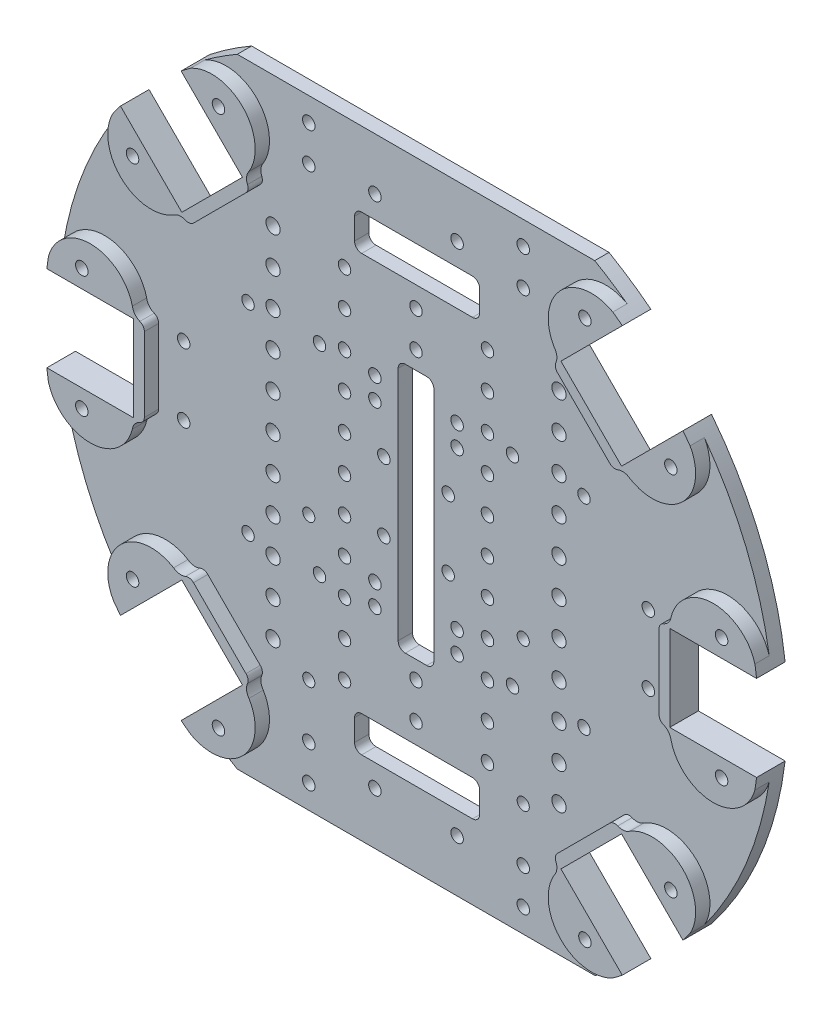
SolidWorks part; units mm, degrees
ref_plane "Front Plane" through (0, 0, 0) normal (0, 0, 1) x (1, 0, 0)
ref_plane "Top Plane" through (0, 0, 0) normal (0, 1, 0) x (1, 0, 0)
ref_plane "Right Plane" through (0, 0, 0) normal (1, 0, 0) x (0, 0, -1)
sketch "Sketch1" plane through (0, 0, 0) normal (0, 0, 1) x (1, 0, 0)
  line L0 (0, 0) -> (0, 100) construction
  line L5 (44.5477, 61.5183) -> (61.7144, 78.685)
  line L6 (44.5477, 61.5183) -> (61.5183, 44.5477)
  line L7 (-12, 75) -> (12, 75) construction
  line L8 (-12, 75) -> (-12, 99.2774) construction
  line L9 (12, 75) -> (12, 99.2774) construction
  line L10 (-17, 89.5) -> (17, 89.5) construction
  line L11 (61.5183, 44.5477) -> (78.685, 61.7144)
  line L12 (75, 12) -> (99.2774, 12)
  line L13 (75, 12) -> (75, -12)
  line L14 (75, -12) -> (99.2774, -12)
  line L15 (61.5183, -44.5477) -> (78.685, -61.7144)
  line L16 (61.5183, -44.5477) -> (44.5477, -61.5183)
  line L17 (44.5477, -61.5183) -> (61.7144, -78.685)
  line L18 (12, -75) -> (12, -99.2774) construction
  line L19 (12, -75) -> (-12, -75) construction
  line L20 (-12, -75) -> (-12, -99.2774) construction
  line L21 (-44.5477, -61.5183) -> (-61.7144, -78.685)
  line L22 (-44.5477, -61.5183) -> (-61.5183, -44.5477)
  line L23 (-61.5183, -44.5477) -> (-78.685, -61.7144)
  line L24 (-75, -12) -> (-99.2774, -12)
  line L25 (-75, -12) -> (-75, 12)
  line L26 (-75, 12) -> (-99.2774, 12)
  line L27 (-61.5183, 44.5477) -> (-78.685, 61.7144)
  line L28 (-61.5183, 44.5477) -> (-44.5477, 61.5183)
  line L29 (-44.5477, 61.5183) -> (-61.7144, 78.685)
  circle A1 centre (0, 0) radius 100
  circle A2 centre (-17, 89.5) radius 1.75 construction
  circle A3 centre (17, 89.5) radius 1.75 construction
  circle A4 centre (51.2652, 75.3069) radius 1.75
  circle A5 centre (75.3069, 51.2652) radius 1.75
  circle A6 centre (89.5, 17) radius 1.75
  circle A7 centre (89.5, -17) radius 1.75
  circle A8 centre (75.3069, -51.2652) radius 1.75
  circle A9 centre (51.2652, -75.3069) radius 1.75
  circle A10 centre (17, -89.5) radius 1.75 construction
  circle A11 centre (-17, -89.5) radius 1.75 construction
  circle A12 centre (-51.2652, -75.3069) radius 1.75
  circle A13 centre (-75.3069, -51.2652) radius 1.75
  circle A14 centre (-89.5, -17) radius 1.75
  circle A15 centre (-89.5, 17) radius 1.75
  circle A16 centre (-75.3069, 51.2652) radius 1.75
  circle A17 centre (-51.2652, 75.3069) radius 1.75
  point P2 (0, 89.5)
  point P4 (0, 75)
  point P12 (0, 75)
  point P19 (0, 89.5)
  dimension "150" = 200
  dimension "D7" = 3.5
  dimension "D2" = 25
  dimension "D3" = 8
  dimension "D4" = 24
  dimension "D5" = 14.5
  dimension "D6" = 34
extrude "Boss-Extrude1" add sketch "Sketch1" along normal blind 4 contours L12 A1 L11 L6 L5 L29 L28 L27 L26 L25 L24 L23 L22 L21 L17 L16 L15 L14 L13 A15 A14 A9 A8 A5 A4 A6 A7 A12 A13 A16 A17 region at (0, 0, 0)
sketch "Sketch2" plane through (0, 0, 4) normal (0, 0, 1) x (1, 0, 0)
  line L0 (0, 35) -> (0, -35) construction
  line L1 (-35, 35) -> (35, 35) construction
  line L2 (-35, 35) -> (-35, -35) construction
  line L3 (-35, -35) -> (35, -35) construction
  line L4 (35, 35) -> (35, -35) construction
  line L5 (-35, 35) -> (35, -35) construction
  line L6 (-35, -35) -> (35, 35) construction
  line L7 (0, 35) -> (0, 80)
  line L8 (-30, -15) -> (30, -15) construction
  line L9 (-30, -15) -> (-30, -55) construction
  line L10 (-30, -55) -> (30, -55) construction
  line L11 (30, -15) -> (30, -55) construction
  line L12 (-30, -15) -> (30, -55) construction
  line L13 (-30, -55) -> (30, -15) construction
  line L14 (-30, 80) -> (30, 80)
  line L15 (0, -55) -> (0, -80)
  line L16 (30, -80) -> (-30, -80)
  line L17 (0, 0) -> (-40, 0) construction
  line L18 (0, 0) -> (40, 0) construction
  line L19 (0, 10) -> (-40, 10)
  line L20 (0, 10) -> (40, 10)
  line L21 (0, 20) -> (-40, 20)
  line L22 (0, 20) -> (40, 20)
  line L23 (0, 30) -> (-40, 30)
  line L24 (0, 30) -> (40, 30)
  line L25 (0, 40) -> (-40, 40)
  line L26 (0, 40) -> (40, 40)
  line L27 (0, 50) -> (-40, 50)
  line L28 (0, 50) -> (40, 50)
  line L29 (0, -10) -> (40, -10)
  line L30 (0, -10) -> (-40, -10)
  line L31 (0, -20) -> (40, -20)
  line L32 (0, -20) -> (-40, -20)
  line L33 (0, -30) -> (40, -30)
  line L34 (0, -30) -> (-40, -30)
  line L35 (0, -40) -> (40, -40)
  line L36 (0, -40) -> (-40, -40)
  line L37 (0, -50) -> (40, -50)
  line L38 (0, -50) -> (-40, -50)
  line L39 (30, -70) -> (-30, -70)
  line L40 (-30, 70) -> (30, 70)
  circle A0 centre (0, 0) radius 100
  circle A1 centre (-30, -55) radius 1.7
  circle A2 centre (-30, -15) radius 1.7
  circle A3 centre (30, -55) radius 1.7
  circle A4 centre (30, -15) radius 1.7
  circle A5 centre (-30, 80) radius 1.75
  circle A6 centre (30, 80) radius 1.75
  circle A7 centre (-30, -80) radius 1.75
  circle A8 centre (30, -80) radius 1.75
  circle A9 centre (-40, 0) radius 2
  circle A10 centre (-20, 0) radius 1.75
  circle A11 centre (0, 0) radius 1.75
  circle A12 centre (40, 0) radius 2
  circle A13 centre (20, 0) radius 1.75
  circle A14 centre (20, 10) radius 1.75
  circle A15 centre (40, 10) radius 2
  circle A16 centre (-20, 10) radius 1.75
  circle A17 centre (-40, 10) radius 2
  circle A18 centre (0, 10) radius 1.75
  circle A19 centre (20, 20) radius 1.75
  circle A20 centre (40, 20) radius 2
  circle A21 centre (-20, 20) radius 1.75
  circle A22 centre (-40, 20) radius 2
  circle A23 centre (0, 20) radius 1.75
  circle A24 centre (20, 30) radius 1.75
  circle A25 centre (40, 30) radius 2
  circle A26 centre (-20, 30) radius 1.75
  circle A27 centre (-40, 30) radius 2
  circle A28 centre (0, 30) radius 1.75
  circle A29 centre (20, 40) radius 1.75
  circle A30 centre (40, 40) radius 2
  circle A31 centre (-20, 40) radius 1.75
  circle A32 centre (-40, 40) radius 2
  circle A33 centre (0, 40) radius 1.75
  circle A34 centre (20, 50) radius 1.75
  circle A35 centre (40, 50) radius 2
  circle A36 centre (-20, 50) radius 1.75
  circle A37 centre (-40, 50) radius 2
  circle A38 centre (0, 50) radius 1.75
  circle A39 centre (40, -10) radius 2
  circle A40 centre (0, -10) radius 1.75
  circle A41 centre (20, -10) radius 1.75
  circle A42 centre (-20, -10) radius 1.75
  circle A43 centre (-40, -10) radius 2
  circle A44 centre (40, -20) radius 2
  circle A45 centre (0, -20) radius 1.75
  circle A46 centre (20, -20) radius 1.75
  circle A47 centre (-20, -20) radius 1.75
  circle A48 centre (-40, -20) radius 2
  circle A49 centre (40, -30) radius 2
  circle A50 centre (0, -30) radius 1.75
  circle A51 centre (20, -30) radius 1.75
  circle A52 centre (-20, -30) radius 1.75
  circle A53 centre (-40, -30) radius 2
  circle A54 centre (40, -40) radius 2
  circle A55 centre (0, -40) radius 1.75
  circle A56 centre (20, -40) radius 1.75
  circle A57 centre (-20, -40) radius 1.75
  circle A58 centre (-40, -40) radius 2
  circle A59 centre (40, -50) radius 2
  circle A60 centre (0, -50) radius 1.75
  circle A61 centre (20, -50) radius 1.75
  circle A62 centre (-20, -50) radius 1.75
  circle A63 centre (-40, -50) radius 2
  circle A64 centre (30, -70) radius 1.75
  circle A65 centre (-30, -70) radius 1.75
  circle A66 centre (-30, 70) radius 1.75
  circle A67 centre (30, 70) radius 1.75
  point P10 (0, 0)
  point P23 (0, 80)
  point P30 (0, -80)
  dimension "D1" = 200
  dimension "D6" = 3.4
  dimension "D9" = 3.5
  dimension "D10" = 3.5
  dimension "D13" = 3.5
  dimension "D14" = 3.5
  dimension "D16" = 4
  dimension "D17" = 3.5
  dimension "D18" = 3.5
  dimension "D2" = 70
  dimension "D3" = 70
  dimension "D4" = 40
  dimension "D5" = 60
  dimension "D7" = 45
  dimension "D8" = 60
  dimension "D11" = 25
  dimension "D12" = 60
  dimension "D15" = 40
  dimension "D19" = 6
  dimension "D20" = 6
  dimension "D21" = 2
  dimension "D22" = 2
extrude "Cut-Extrude1" cut sketch "Sketch2" against normal blind 10 contours A65 | A7 | A8 | A64 | A3 | A59 | A61 L37 | A61 L37 | A63 | L38 A62 | L38 A62 | L37 A60 L38 | L38 A60 L37 | A58 | L36 A57 | L36 A57 | L35 A55 L36 | L36 A55 L35 | A56 L35 | A56 L35 | A54 | A49 | A51 L33 | A51 L33 | L34 A50 L33 | L33 A50 L34 | L34 A52 | L34 A52 | A53 | A48 | L32 A47 | L32 A47 | L31 A45 L32 | L32 A45 L31 | A46 L31 | A46 L31 | A44 | A4 | A2 | L30 A42 | L30 A42 | A43 | L30 A40 L29 | L29 A40 L30 | A41 L29 | A41 L29 | A39 | A12 | A13 | A11 | A9 | A10 | A15 | A14 L20 | A14 L20 | L19 A18 L20 | L20 A18 L19 | L19 A16 | L19 A16 | A17 | A22 | A21 | A23 | A19 | A25 | A30 | A35 | A29 | A33 | A31 | A32 | A27 | A26 | A28 | A24 | A20 | A38 | A36 | A37 | A34 | A1 | A6 | A67 | A66 | A5 region at (30, -78.2995, 4) region at (-31.7005, -80, 4) region at (30, -68.2995, 4) region at (-31.7005, -70, 4) region at (0, 9.2573, 4) region at (0, 10.7427, 4) region at (-41.9434, 10, 4) region at (-20, 9.2573, 4) region at (-20, 10.7427, 4) region at (40, 11.9434, 4) region at (20, 10.7427, 4) region at (20, 9.2573, 4) region at (0, -9.2573, 4) region at (0, -10.7427, 4) region at (40, -8.0566, 4) region at (20, -9.2573, 4) region at (20, -10.7427, 4) region at (-41.9434, -10, 4) region at (-20, -10.7427, 4) region at (-20, -9.2573, 4) region at (0, -19.2573, 4) region at (0, -20.7427, 4) region at (40, -18.0566, 4) region at (20, -19.2573, 4) region at (20, -20.7427, 4) region at (-41.9434, -20, 4) region at (-20, -20.7427, 4) region at (-20, -19.2573, 4) region at (0, -29.2573, 4) region at (0, -30.7427, 4) region at (40, -28.0566, 4) region at (20, -29.2573, 4) region at (20, -30.7427, 4) region at (-41.9434, -30, 4) region at (-20, -30.7427, 4) region at (-20, -29.2573, 4) region at (0, -39.2573, 4) region at (0, -40.7427, 4) region at (40, -38.0566, 4) region at (20, -39.2573, 4) region at (20, -40.7427, 4) region at (-41.9434, -40, 4) region at (-20, -40.7427, 4) region at (-20, -39.2573, 4) region at (0, -49.2573, 4) region at (0, -50.7427, 4) region at (40, -48.0566, 4) region at (20, -49.2573, 4) region at (20, -50.7427, 4) region at (-41.9434, -50, 4) region at (-20, -50.7427, 4) region at (-20, -49.2573, 4) region at (-30, -15, 4) region at (30, -55, 4) region at (30, -15, 4) region at (-40, 0, 4) region at (-20, 0, 4) region at (0, 0, 4) region at (40, 0, 4) region at (20, 0, 4)
sketch "Sketch3" plane through (0, 0, 4) normal (0, 0, 1) x (1, 0, 0)
  line L0 (-78.685, 61.7144) -> (-61.5183, 44.5477)
  line L1 (-61.5183, 44.5477) -> (-44.5477, 61.5183)
  line L2 (-44.5477, 61.5183) -> (-61.7144, 78.685)
  line L3 (-58.255, 43.5684) -> (-43.5684, 58.255)
  line L4 (-53.033, 53.033) -> (-50.9117, 50.9117)
  line L5 (-10.385, 72) -> (10.385, 72)
  line L6 (-12, 75) -> (12, 75)
  line L7 (-12, 99.2774) -> (-12, 75)
  line L8 (12, 75) -> (12, 99.2774)
  line L9 (43.5684, 58.255) -> (58.255, 43.5684)
  line L10 (44.5477, 61.5183) -> (61.5183, 44.5477)
  line L11 (61.7144, 78.685) -> (44.5477, 61.5183)
  line L12 (61.5183, 44.5477) -> (78.685, 61.7144)
  line L13 (72, 10.385) -> (72, -10.385)
  line L14 (75, 12) -> (75, -12)
  line L15 (99.2774, 12) -> (75, 12)
  line L16 (75, -12) -> (99.2774, -12)
  line L17 (58.255, -43.5684) -> (43.5684, -58.255)
  line L18 (61.5183, -44.5477) -> (44.5477, -61.5183)
  line L19 (78.685, -61.7144) -> (61.5183, -44.5477)
  line L20 (44.5477, -61.5183) -> (61.7144, -78.685)
  line L21 (10.385, -72) -> (-10.385, -72)
  line L22 (12, -75) -> (-12, -75)
  line L23 (12, -99.2774) -> (12, -75)
  line L24 (-12, -75) -> (-12, -99.2774)
  line L25 (-43.5684, -58.255) -> (-58.255, -43.5684)
  line L26 (-44.5477, -61.5183) -> (-61.5183, -44.5477)
  line L27 (-61.7144, -78.685) -> (-44.5477, -61.5183)
  line L28 (-61.5183, -44.5477) -> (-78.685, -61.7144)
  line L29 (-72, -10.385) -> (-72, 10.385)
  line L30 (-75, -12) -> (-75, 12)
  line L31 (-99.2774, -12) -> (-75, -12)
  line L32 (-75, 12) -> (-99.2774, 12)
  arc A1 (-12.2421, 73.2574) -> (-10.385, 72) centre (-10.385, 74) ccw
  circle A2 centre (0, 0) radius 100
  arc A3 (-61.5183, 44.5477) -> (-78.685, 61.7144) centre (-70.1016, 53.1311) cw
  arc A4 (-61.7144, 78.685) -> (-44.5477, 61.5183) centre (-53.1311, 70.1016) cw
  circle A5 centre (-51.2652, 75.3069) radius 1.75
  circle A6 centre (-75.3069, 51.2652) radius 1.75
  arc A7 (-43.1444, 60.4573) -> (-42.7452, 63.8182) centre (-40.0316, 61.7918) cw
  arc A8 (-60.4573, 43.1444) -> (-63.8182, 42.7452) centre (-61.7918, 40.0316) ccw
  arc A9 (-60.4573, 43.1444) -> (-58.255, 43.5684) centre (-59.6692, 44.9826) ccw
  arc A10 (-43.1444, 60.4573) -> (-43.5684, 58.255) centre (-44.9826, 59.6692) cw
  arc A11 (-12.2421, 73.2574) -> (-14.9009, 75.3517) centre (-15.3867, 72) ccw
  arc A12 (-12, 75) -> (-12, 99.2774) centre (-12, 87.1387) cw
  circle A13 centre (-17, 89.5) radius 1.75
  circle A14 centre (17, 89.5) radius 1.75
  arc A15 (12, 99.2774) -> (12, 75) centre (12, 87.1387) cw
  arc A16 (12.2421, 73.2574) -> (14.9009, 75.3517) centre (15.3867, 72) cw
  arc A17 (12.2421, 73.2574) -> (10.385, 72) centre (10.385, 74) cw
  arc A18 (43.1444, 60.4573) -> (43.5684, 58.255) centre (44.9826, 59.6692) ccw
  arc A19 (43.1444, 60.4573) -> (42.7452, 63.8182) centre (40.0316, 61.7918) ccw
  arc A20 (44.5477, 61.5183) -> (61.7144, 78.685) centre (53.1311, 70.1016) cw
  circle A21 centre (51.2652, 75.3069) radius 1.75
  circle A22 centre (75.3069, 51.2652) radius 1.75
  arc A23 (78.685, 61.7144) -> (61.5183, 44.5477) centre (70.1016, 53.1311) cw
  arc A24 (60.4573, 43.1444) -> (63.8182, 42.7452) centre (61.7918, 40.0316) cw
  arc A25 (60.4573, 43.1444) -> (58.255, 43.5684) centre (59.6692, 44.9826) cw
  arc A26 (73.2574, 12.2421) -> (72, 10.385) centre (74, 10.385) ccw
  arc A27 (73.2574, 12.2421) -> (75.3517, 14.9009) centre (72, 15.3867) ccw
  arc A28 (75, 12) -> (99.2774, 12) centre (87.1387, 12) cw
  circle A29 centre (89.5, 17) radius 1.75
  circle A30 centre (89.5, -17) radius 1.75
  arc A31 (99.2774, -12) -> (75, -12) centre (87.1387, -12) cw
  arc A32 (73.2574, -12.2421) -> (75.3517, -14.9009) centre (72, -15.3867) cw
  arc A33 (73.2574, -12.2421) -> (72, -10.385) centre (74, -10.385) cw
  arc A34 (60.4573, -43.1444) -> (58.255, -43.5684) centre (59.6692, -44.9826) ccw
  arc A35 (60.4573, -43.1444) -> (63.8182, -42.7452) centre (61.7918, -40.0316) ccw
  arc A36 (61.5183, -44.5477) -> (78.685, -61.7144) centre (70.1016, -53.1311) cw
  circle A37 centre (75.3069, -51.2652) radius 1.75
  circle A38 centre (51.2652, -75.3069) radius 1.75
  arc A39 (61.7144, -78.685) -> (44.5477, -61.5183) centre (53.1311, -70.1016) cw
  arc A40 (43.1444, -60.4573) -> (42.7452, -63.8182) centre (40.0316, -61.7918) cw
  arc A41 (43.1444, -60.4573) -> (43.5684, -58.255) centre (44.9826, -59.6692) cw
  arc A42 (12.2421, -73.2574) -> (10.385, -72) centre (10.385, -74) ccw
  arc A43 (12.2421, -73.2574) -> (14.9009, -75.3517) centre (15.3867, -72) ccw
  arc A44 (12, -75) -> (12, -99.2774) centre (12, -87.1387) cw
  circle A45 centre (17, -89.5) radius 1.75
  circle A46 centre (-17, -89.5) radius 1.75
  arc A47 (-12, -99.2774) -> (-12, -75) centre (-12, -87.1387) cw
  arc A48 (-12.2421, -73.2574) -> (-14.9009, -75.3517) centre (-15.3867, -72) cw
  arc A49 (-12.2421, -73.2574) -> (-10.385, -72) centre (-10.385, -74) cw
  arc A50 (-43.1444, -60.4573) -> (-43.5684, -58.255) centre (-44.9826, -59.6692) ccw
  arc A51 (-43.1444, -60.4573) -> (-42.7452, -63.8182) centre (-40.0316, -61.7918) ccw
  arc A52 (-44.5477, -61.5183) -> (-61.7144, -78.685) centre (-53.1311, -70.1016) cw
  circle A53 centre (-51.2652, -75.3069) radius 1.75
  circle A54 centre (-75.3069, -51.2652) radius 1.75
  arc A55 (-78.685, -61.7144) -> (-61.5183, -44.5477) centre (-70.1016, -53.1311) cw
  arc A56 (-60.4573, -43.1444) -> (-63.8182, -42.7452) centre (-61.7918, -40.0316) cw
  arc A57 (-60.4573, -43.1444) -> (-58.255, -43.5684) centre (-59.6692, -44.9826) cw
  arc A58 (-73.2574, -12.2421) -> (-72, -10.385) centre (-74, -10.385) ccw
  arc A59 (-73.2574, -12.2421) -> (-75.3517, -14.9009) centre (-72, -15.3867) ccw
  arc A60 (-75, -12) -> (-99.2774, -12) centre (-87.1387, -12) cw
  circle A61 centre (-89.5, -17) radius 1.75
  circle A62 centre (-89.5, 17) radius 1.75
  arc A63 (-99.2774, 12) -> (-75, 12) centre (-87.1387, 12) cw
  arc A64 (-73.2574, 12.2421) -> (-75.3517, 14.9009) centre (-72, 15.3867) cw
  arc A65 (-73.2574, 12.2421) -> (-72, 10.385) centre (-74, 10.385) cw
  point P29 (-59.397, 42.4264)
  point P32 (-42.4264, 59.397)
  dimension "D2" = 2
  dimension "D1" = 2
  dimension "D3" = 8
extrude "Boss-Extrude2" add sketch "Sketch3" along normal blind 4 contours A39 A40 A2 L20 A38 | A41 A40 A39 L18 A36 A35 A34 L17 | A36 L19 A2 A35 A37 | A31 A32 A2 L16 A30 | A33 A32 A31 L14 A28 A27 A26 L13 | A28 L15 A2 A27 A29 | A23 A24 A2 L12 A22 | A25 A24 A23 L10 A20 A19 A18 L9 | A20 L11 A2 A19 A21 | A4 A7 A2 L2 A5 | A10 A7 A4 L1 L4 L3 | A8 A9 L3 L4 L1 A3 | A8 A3 L0 A2 A6 | A63 A64 A2 L32 A62 | A65 A64 A63 L30 A60 A59 A58 L29 | A60 L31 A2 A59 A61 | A55 A56 A2 L28 A54 | A57 A56 A55 L26 A52 A51 A50 L25 | A52 L27 A2 A51 A53 region at (-73.6709, 49.4003, 4) region at (-56.4143, 47.6048, 4) region at (-49.4003, 73.6709, 4) region at (-47.6048, 56.4143, 4) region at (-87.0245, 17.1619, 4) region at (-73.5526, 0, 4) region at (-87.0245, -17.1619, 4) region at (-73.6709, -49.4003, 4) region at (49.4003, 73.6709, 4) region at (-52.0095, -52.0095, 4) region at (-49.4003, -73.6709, 4) region at (52.0095, 52.0095, 4) region at (73.6709, 49.4003, 4) region at (87.0245, 17.1619, 4) region at (73.5526, 0, 4) region at (87.0245, -17.1619, 4) region at (49.4003, -73.6709, 4) region at (73.6709, -49.4003, 4) region at (52.0095, -52.0095, 4)
sketch "Sketch4" plane through (0, 0, 0) normal (0, 0, -1) x (-1, 0, 0)
  line L0 (-11.5, 72) -> (-11.5, 28)
  line L1 (-11.5, 22) -> (11.5, 22) construction
  line L2 (-11.5, 22) -> (-11.5, -22) construction
  line L3 (-11.5, -22) -> (11.5, -22) construction
  line L4 (11.5, 22) -> (11.5, -22) construction
  line L5 (-11.5, 22) -> (11.5, -22) construction
  line L6 (-11.5, -22) -> (11.5, 22) construction
  line L7 (-11.5, 72) -> (11.5, 72)
  line L8 (11.5, 72) -> (11.5, 28)
  line L9 (-11.5, 28) -> (11.5, 28)
  line L10 (-11.5, 22) -> (-11.5, -22)
  line L11 (-11.5, 22) -> (11.5, 22)
  line L12 (11.5, 22) -> (11.5, -22)
  line L13 (-11.5, -22) -> (11.5, -22)
  line L14 (-11.5, -28) -> (-11.5, -72)
  line L15 (-11.5, -28) -> (11.5, -28)
  line L16 (11.5, -28) -> (11.5, -72)
  line L17 (-11.5, -72) -> (11.5, -72)
  line L18 (0, 0) -> (100, 0)
  line L19 (-47, 28) -> (-47, -28)
  line L20 (35, 28) -> (55, 28) construction
  line L21 (35, 28) -> (35, -28) construction
  line L22 (35, -28) -> (55, -28) construction
  line L23 (55, 28) -> (55, -28) construction
  line L24 (35, 28) -> (55, -28) construction
  line L25 (35, -28) -> (55, 28) construction
  line L26 (-47, 28) -> (-27, 28)
  line L27 (-27, 28) -> (-27, -28)
  line L28 (-47, -28) -> (-27, -28)
  line L29 (0, 22) -> (0, -22)
  line L30 (47, 28) -> (27, 28)
  line L31 (27, 28) -> (27, -28)
  line L32 (47, -28) -> (27, -28)
  line L33 (47, 28) -> (47, -28)
  circle A0 centre (0, 0) radius 100
  circle A1 centre (-11.5, 22) radius 1.75
  circle A2 centre (11.5, 22) radius 1.75
  circle A3 centre (11.5, -22) radius 1.75
  circle A4 centre (-11.5, -22) radius 1.75
  circle A5 centre (11.5, 72) radius 1.75
  circle A6 centre (-11.5, 72) radius 1.75
  circle A7 centre (-11.5, 28) radius 1.75
  circle A8 centre (11.5, 28) radius 1.75
  circle A9 centre (11.5, 22) radius 1.75
  circle A10 centre (-11.5, 22) radius 1.75
  circle A11 centre (-11.5, -22) radius 1.75
  circle A12 centre (11.5, -22) radius 1.75
  circle A13 centre (11.5, -28) radius 1.75
  circle A14 centre (-11.5, -28) radius 1.75
  circle A15 centre (-11.5, -72) radius 1.75
  circle A16 centre (11.5, -72) radius 1.75
  circle A17 centre (35, 28) radius 1.75 construction
  circle A18 centre (55, 28) radius 1.75 construction
  circle A19 centre (55, -28) radius 1.75 construction
  circle A20 centre (35, -28) radius 1.75 construction
  circle A21 centre (-47, 28) radius 1.75
  circle A22 centre (-27, 28) radius 1.75
  circle A23 centre (-47, -28) radius 1.75
  circle A24 centre (-27, -28) radius 1.75
  circle A25 centre (47, 28) radius 1.75
  circle A26 centre (27, 28) radius 1.75
  circle A27 centre (47, -28) radius 1.75
  circle A28 centre (27, -28) radius 1.75
  point P11 (45, 0)
  point P13 (45, 0)
  dimension "D3" = 3.5
  dimension "D9" = 3.5
  dimension "D1" = 44
  dimension "D2" = 23
  dimension "D6" = 45
  dimension "D7" = 56
  dimension "D8" = 20
  dimension "D4" = 2
  dimension "D5" = 2
  dimension "D10" = 2
extrude "Cut-Extrude2" cut sketch "Sketch4" against normal blind 10 contours L8 A5 L7 | L7 A5 L8 | L7 A6 L0 | L0 A6 L7 | L0 A7 L9 | L9 A7 L0 | L9 A8 L8 | L8 A8 L9 | L12 A2 L11 | L11 A2 L12 | L11 A1 L10 | L10 A1 L11 | L12 A3 L13 | L13 A3 L12 | L13 A4 L10 | L10 A4 L13 | L15 A14 L14 | L14 A14 L15 | L15 A13 L16 | L16 A13 L15 | L14 A15 L17 | L17 A15 L14 | L17 A16 L16 | L16 A16 L17 | L26 A21 L19 | L19 A21 L26 | L26 A22 L27 | L27 A22 L26 | L28 A24 L27 | L27 A24 L28 | L19 A23 L28 | L28 A23 L19 | A25 L30 L33 | A25 L33 L30 | A26 L30 L31 | A26 L31 L30 | A27 L33 L32 | A27 L32 L33 | A28 L32 L31 | A28 L31 L32 region at (10.7573, 71.2573, 0) region at (11.7476, 72.2476, 0) region at (10.7573, 28.7427, 0) region at (11.7476, 27.7524, 0) region at (-11.7476, 72.2476, 0) region at (-10.7573, 71.2573, 0) region at (-10.7573, 28.7427, 0) region at (-11.7476, 27.7524, 0) region at (10.7573, 21.2573, 0) region at (11.7476, 22.2476, 0) region at (10.7573, -21.2573, 0) region at (11.7476, -22.2476, 0) region at (-11.7476, 22.2476, 0) region at (-10.7573, 21.2573, 0) region at (-10.7573, -21.2573, 0) region at (-11.7476, -22.2476, 0) region at (-26.7524, 28.2476, 0) region at (-27.7427, 27.2573, 0) region at (-27.7427, -27.2573, 0) region at (-26.7524, -28.2476, 0) region at (-46.2573, 27.2573, 0) region at (-47.2476, 28.2476, 0) region at (-47.2476, -28.2476, 0) region at (-46.2573, -27.2573, 0) region at (10.7573, -28.7427, 0) region at (11.7476, -27.7524, 0) region at (10.7573, -71.2573, 0) region at (11.7476, -72.2476, 0) region at (-11.7476, -27.7524, 0) region at (-10.7573, -28.7427, 0) region at (-10.7573, -71.2573, 0) region at (-11.7476, -72.2476, 0) region at (46.2573, 27.2573, 0) region at (47.2476, 28.2476, 0) region at (46.2573, -27.2573, 0) region at (47.2476, -28.2476, 0) region at (26.7524, 28.2476, 0) region at (27.7427, 27.2573, 0) region at (27.7427, -27.2573, 0) region at (26.7524, -28.2476, 0)
sketch "Sketch5" plane through (0, 0, 0) normal (0, 0, -1) x (-1, 0, 0)
  line L0 (9, 9.6) -> (9, -9.6) construction
  line L1 (-3, 35) -> (3, 35)
  line L2 (-5, 33) -> (-5, -33)
  line L3 (-3, -35) -> (3, -35)
  line L4 (5, 33) -> (5, -33)
  line L5 (-5, 35) -> (5, -35) construction
  line L6 (-5, -35) -> (5, 35) construction
  line L7 (-28, 9.6) -> (28, 9.6) construction
  line L8 (-28, 9.6) -> (-28, -9.6) construction
  line L9 (-28, -9.6) -> (28, -9.6) construction
  line L10 (28, 9.6) -> (28, -9.6) construction
  line L11 (-28, 9.6) -> (28, -9.6) construction
  line L12 (-28, -9.6) -> (28, 9.6) construction
  line L13 (9, 9.6) -> (65, 9.6) construction
  line L14 (65, 9.6) -> (65, -9.6) construction
  line L15 (9, -9.6) -> (65, -9.6) construction
  line L16 (0, 35) -> (0, 0) construction
  line L17 (0, 0) -> (5, 0) construction
  line L18 (-15.8022, -55.7522) -> (15.1978, -55.7522)
  line L19 (-17.8022, -57.7522) -> (-17.8022, -63.7522)
  line L20 (-15.8022, -65.7522) -> (15.1978, -65.7522)
  line L21 (17.1978, -57.7522) -> (17.1978, -63.7522)
  line L22 (-17.8022, -55.7522) -> (17.1978, -65.7522) construction
  line L23 (-17.8022, -65.7522) -> (17.1978, -55.7522) construction
  line L24 (-15.8022, 65.7522) -> (15.1978, 65.7522)
  line L25 (17.1978, 57.7522) -> (17.1978, 63.7522)
  line L26 (-15.8022, 55.7522) -> (15.1978, 55.7522)
  line L27 (-17.8022, 57.7522) -> (-17.8022, 63.7522)
  circle A0 centre (0, 0) radius 100
  arc A1 (17.1978, -57.7522) -> (15.1978, -55.7522) centre (15.1978, -57.7522) ccw
  arc A2 (3, -35) -> (5, -33) centre (3, -33) ccw
  arc A3 (-3, -35) -> (-5, -33) centre (-3, -33) cw
  arc A4 (3, 35) -> (5, 33) centre (3, 33) cw
  arc A5 (-3, 35) -> (-5, 33) centre (-3, 33) ccw
  circle A6 centre (-28, 9.6) radius 1.75 construction
  circle A7 centre (-28, -9.6) radius 1.75 construction
  circle A8 centre (28, 9.6) radius 1.75 construction
  circle A9 centre (28, -9.6) radius 1.75 construction
  circle A10 centre (9, 9.6) radius 1.75
  circle A11 centre (9, -9.6) radius 1.75
  circle A12 centre (65, 9.6) radius 1.75
  circle A13 centre (65, -9.6) radius 1.75
  circle A14 centre (-9, 9.6) radius 1.75
  circle A15 centre (-9, -9.6) radius 1.75
  circle A16 centre (-65, -9.6) radius 1.75
  circle A17 centre (-65, 9.6) radius 1.75
  arc A18 (17.1978, -63.7522) -> (15.1978, -65.7522) centre (15.1978, -63.7522) cw
  arc A19 (-17.8022, -63.7522) -> (-15.8022, -65.7522) centre (-15.8022, -63.7522) ccw
  arc A20 (-15.8022, -55.7522) -> (-17.8022, -57.7522) centre (-15.8022, -57.7522) ccw
  arc A21 (17.1978, 63.7522) -> (15.1978, 65.7522) centre (15.1978, 63.7522) ccw
  arc A22 (17.1978, 57.7522) -> (15.1978, 55.7522) centre (15.1978, 57.7522) cw
  arc A23 (-17.8022, 63.7522) -> (-15.8022, 65.7522) centre (-15.8022, 63.7522) cw
  arc A24 (-15.8022, 55.7522) -> (-17.8022, 57.7522) centre (-15.8022, 57.7522) cw
  point P44 (-0.3022, -60.7522)
  dimension "D3" = 2
  dimension "D6" = 3.5
  dimension "D10" = 2
  dimension "D1" = 70
  dimension "D2" = 10
  dimension "D4" = 19.2
  dimension "D5" = 56
  dimension "D8" = 10
  dimension "D9" = 35
  dimension "D7" = 2
extrude "Cut-Extrude4" cut sketch "Sketch5" against normal blind 10 contours A5 L1 A4 L4 A2 L3 A3 L2 | A14 | A10 | A11 | A15 | A17 | A16 | A12 | A13 | L19 A19 L20 A18 L21 A1 L18 A20 | L24 A21 L25 A22 L26 A24 L27 A23
sketch "Sketch6" plane through (0, 0, 4) normal (0, 0, 1) x (1, 0, 0)
  line L0 (0, 0) -> (0, -100) construction
  line L1 (-50, -86.6025) -> (50, -86.6025)
  line L2 (0, 0) -> (-100, 0) construction
  line L4 (-50, 86.6025) -> (50, 86.6025)
  circle A0 centre (0, 0) radius 100
  point P7 (0, -86.6025)
  dimension "D1" = 200
  dimension "D2" = 100
extrude "Cut-Extrude6" cut sketch "Sketch6" against normal blind 10 contours L4 A0 | L1 A0 region at (0, -91.9935, 4) region at (0, 91.9935, 4)
sketch "Sketch7" plane through (8.4853, 8.4853, 0) normal (-0.7071, -0.7071, 0) x (0, 0, 1)
  line L1 (8, 99.2774) -> (0, 99.2774)
  line L2 (8, 99.2774) -> (8, 75)
  line L3 (8, 75) -> (0, 75)
  line L4 (0, 99.2774) -> (0, 75)
  line L5 (2.854, 93.5395) -> (8.0043, 93.5395)
  line L6 (2.854, 93.5395) -> (2.854, 84.9449)
  line L7 (2.854, 84.9449) -> (8.0043, 84.9449)
  line L8 (8.0043, 93.5395) -> (8.0043, 84.9449)
  dimension "D1" = 5.146
